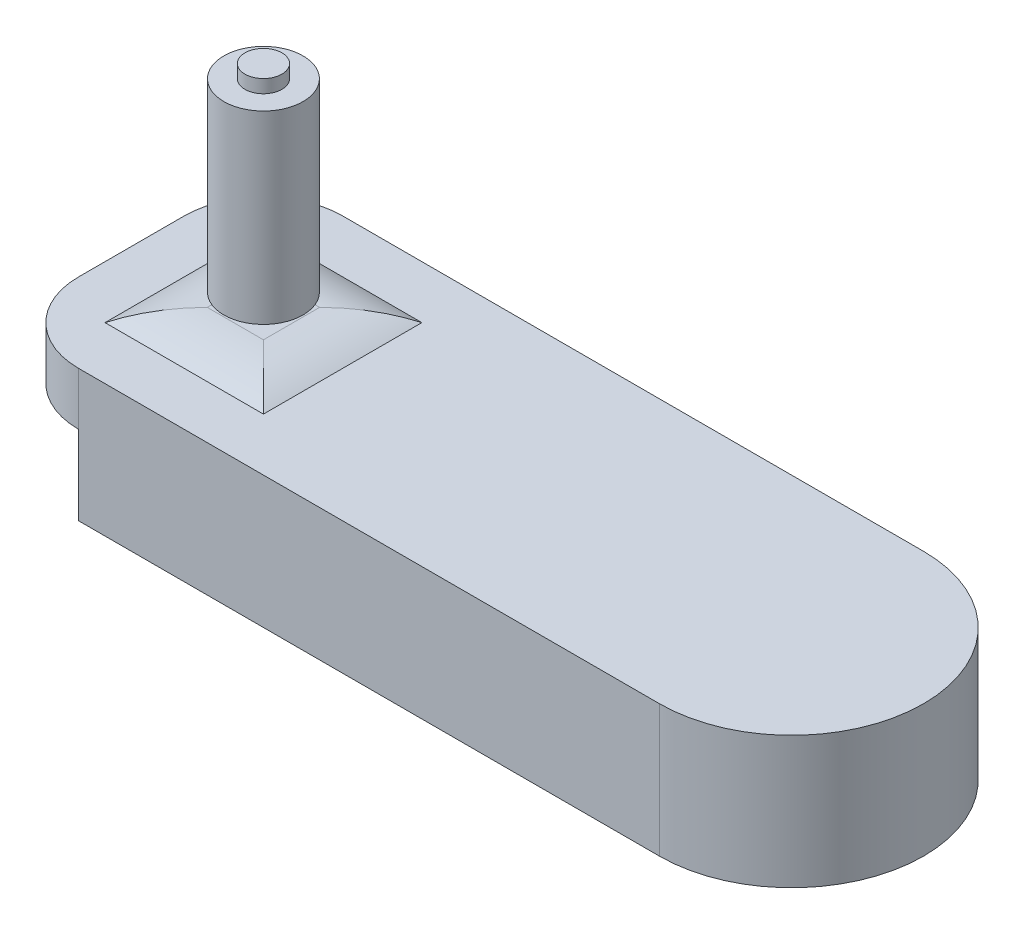
SolidWorks part; units mm, degrees
ref_plane "Front Plane" through (0, 0, 0) normal (0, 0, 1) x (1, 0, 0)
ref_plane "Top Plane" through (0, 0, 0) normal (0, 1, 0) x (1, 0, 0)
ref_plane "Right Plane" through (0, 0, 0) normal (1, 0, 0) x (0, 0, -1)
sketch "Sketch1" plane through (0, 0, 0) normal (0, 1, 0) x (1, 0, 0)
  line L0 (0, 0) -> (-381, 0)
  line L1 (-381, 0) -> (-381, -127)
  line L2 (-381, -127) -> (0, -127)
  line L3 (0, -127) -> (0, 0)
  dimension "D1" = 381
  dimension "D2" = 127
extrude "Boss-Extrude1" add sketch "Sketch1" along normal blind 25.4
fillet "Fillet1" radius 63.5 2 edges at (0, 12.7, 0) (0, 12.7, 127)
fillet "Fillet2" radius 38.1 2 edges at (-381, 12.7, 0) (-381, 12.7, 127)
sketch "Sketch2" plane through (0, 0, 0) normal (0, 1, 0) x (1, 0, 0)
  line L0 (-63.5, -12.7) -> (-342.9, -11.1592)
  line L1 (-342.9, -11.1592) -> (-342.9, 0)
  line L2 (-342.9, 0) -> (-63.5, 0)
  line L3 (-63.5, -127) -> (-342.9, -127)
  line L4 (-342.9, -127) -> (-342.9, -114.3)
  line L5 (-342.9, -114.3) -> (-63.5, -114.3)
  arc A0 (-63.5, -114.3) -> (-63.5, -12.7) centre (-63.5, -63.5) ccw
  arc A1 (-63.5, 0) -> (-63.5, -127) centre (-63.5, -63.5) cw
  arc A2 (-63.5, -127) -> (0, -63.5) centre (-63.5, -63.5) ccw construction
  dimension "D1" = 11.1592
  dimension "D3" = 12.7
  dimension "D2" = 12.7
extrude "Boss-Extrude2" add sketch "Sketch2" against normal blind 25.4
ref_plane "Plane1" through (0, -25.4, 0) normal (0, 1, 0) x (1, 0, 0)
sketch "Sketch3" plane through (0, -25.4, 0) normal (0, 1, 0) x (1, 0, 0)
  line L1 (-342.9, -127) -> (-342.9, -82.55)
  line L2 (-342.9, -114.3) -> (-342.9, -127) construction
  line L3 (-342.9, 0) -> (-342.9, -44.45)
  line L4 (-342.9, 0) -> (-63.5, 0)
  line L5 (-63.5, -44.45) -> (-342.9, -44.45)
  line L6 (-342.9, -82.55) -> (-63.5, -82.55)
  line L7 (-63.5, -127) -> (-342.9, -127)
  arc A0 (-381, -88.9) -> (-342.9, -127) centre (-342.9, -88.9) ccw construction
  arc A1 (-63.5, -127) -> (-63.5, 0) centre (-63.5, -63.5) ccw
  arc A2 (-63.5, -127) -> (-63.5, 0) centre (-63.5, -63.5) ccw construction
  arc A3 (-63.5, -82.55) -> (-63.5, -44.45) centre (-63.5, -63.5) ccw
  dimension "D1" = 44.45
  dimension "D2" = 44.45
  dimension "D3" = 279.4
extrude "Boss-Extrude3" add sketch "Sketch3" against normal blind 12.7
sketch "Sketch4" plane through (0, 25.4, 0) normal (0, 1, 0) x (1, 0, 0)
  line L0 (-355.6, -25.4) -> (-355.6, -101.6)
  line L2 (-355.6, -25.4) -> (-279.4, -25.4)
  line L5 (-355.6, -101.6) -> (-279.4, -101.6)
  line L6 (-279.4, -25.4) -> (-279.4, -101.6)
  dimension "D1" = 76.2
  dimension "D2" = 76.2
  dimension "D3" = 279.4
  dimension "D4" = 25.4
extrude "Boss-Extrude4" add sketch "Sketch4" along normal blind 6.35
fillet "Fillet3" radius 50.8 4 edges at (-279.4, 31.75, 63.5) (-317.5, 31.75, 101.6) (-355.6, 31.75, 63.5) (-317.5, 31.75, 25.4)
sketch "Sketch5" plane through (0, 31.75, 0) normal (0, 1, 0) x (1, 0, 0)
  circle A0 centre (-317.5, -63.5) radius 8.89
  dimension "D1" = 17.78
  dimension "D2" = 317.5
  dimension "D3" = 63.5
extrude "Boss-Extrude5" add sketch "Sketch5" along normal blind 6.35
sketch "Sketch6" plane through (0, 38.1, 0) normal (0, 1, 0) x (1, 0, 0)
  circle A1 centre (-317.5, -63.5) radius 19.05
  dimension "D1" = 38.1
extrude "Boss-Extrude6" add sketch "Sketch6" along normal blind 88.9
sketch "Sketch7" plane through (0, 0, 0) normal (0, 0, 1) x (1, 0, 0)
  line L0 (-336.55, 127) -> (-336.55, 124.46)
  line L1 (-336.55, 127) -> (-336.55, 38.1) construction
  line L2 (-336.55, 105.4219) -> (-336.55, 105.41)
  line L3 (-336.55, 105.41) -> (-336.55, 102.87)
  line L4 (-336.55, 83.8319) -> (-336.55, 83.82)
  line L5 (-336.55, 83.82) -> (-336.55, 81.28)
  line L6 (-336.55, 62.2419) -> (-336.55, 62.23)
  line L7 (-336.55, 62.23) -> (-336.55, 59.69)
  line L8 (-336.55, 40.6519) -> (-336.55, 40.64)
  line L9 (-336.55, 40.64) -> (-368.0139, 40.64)
  line L10 (-368.0139, 40.64) -> (-368.0139, 127.71)
  line L11 (-368.0139, 127.71) -> (-336.55, 127)
  arc A0 (-336.55, 102.87) -> (-336.55, 83.8319) centre (-346.0691, 93.3509) cw
  arc A2 (-336.55, 124.46) -> (-336.55, 105.4219) centre (-346.0691, 114.9409) cw
  arc A3 (-336.55, 81.28) -> (-336.55, 62.2419) centre (-346.0691, 71.7609) cw
  arc A4 (-336.55, 59.69) -> (-336.55, 40.6519) centre (-346.0691, 50.1709) cw
  dimension "D1" = 13.462
  dimension "D2" = 346.0691
  dimension "D3" = 368.0139
  dimension "D4" = 40.64
  dimension "D5" = 40.6519
  dimension "D20" = 127.71
extrude "Cut-Extrude1" cut sketch "Sketch7" along normal blind 88.9
sketch "Sketch8" plane through (0, 127, 0) normal (0, 1, 0) x (1, 0, 0)
  circle A0 centre (-317.5, -63.5) radius 8.89
  dimension "D1" = 17.78
extrude "Boss-Extrude7" add sketch "Sketch8" along normal blind 6.35
sketch "Sketch9" plane through (0, 0, 0) normal (0, -1, 0) x (1, 0, 0)
  line L0 (-342.9, 82.55) -> (-63.5, 82.55)
  line L1 (-63.5, 44.45) -> (-342.9, 44.45)
  line L2 (-342.9, 0) -> (-342.9, 44.45) construction
  line L3 (-342.9, 44.45) -> (-63.5, 44.45) construction
  line L4 (-342.9, 44.45) -> (-342.9, 82.55)
  arc A0 (-63.5, 82.55) -> (-63.5, 44.45) centre (-63.5, 63.5) cw
  arc A1 (-63.5, 44.45) -> (-63.5, 82.55) centre (-63.5, 63.5) ccw construction
extrude "Cut-Extrude2" cut sketch "Sketch9" against normal blind 12.7
sketch "Sketch10" plane through (0, 12.7, 0) normal (0, -1, 0) x (1, 0, 0)
  circle A0 centre (-317.5, 63.5) radius 5.08
  dimension "D1" = 10.16
extrude "Cut-Extrude3" cut sketch "Sketch10" against normal blind 95.25
